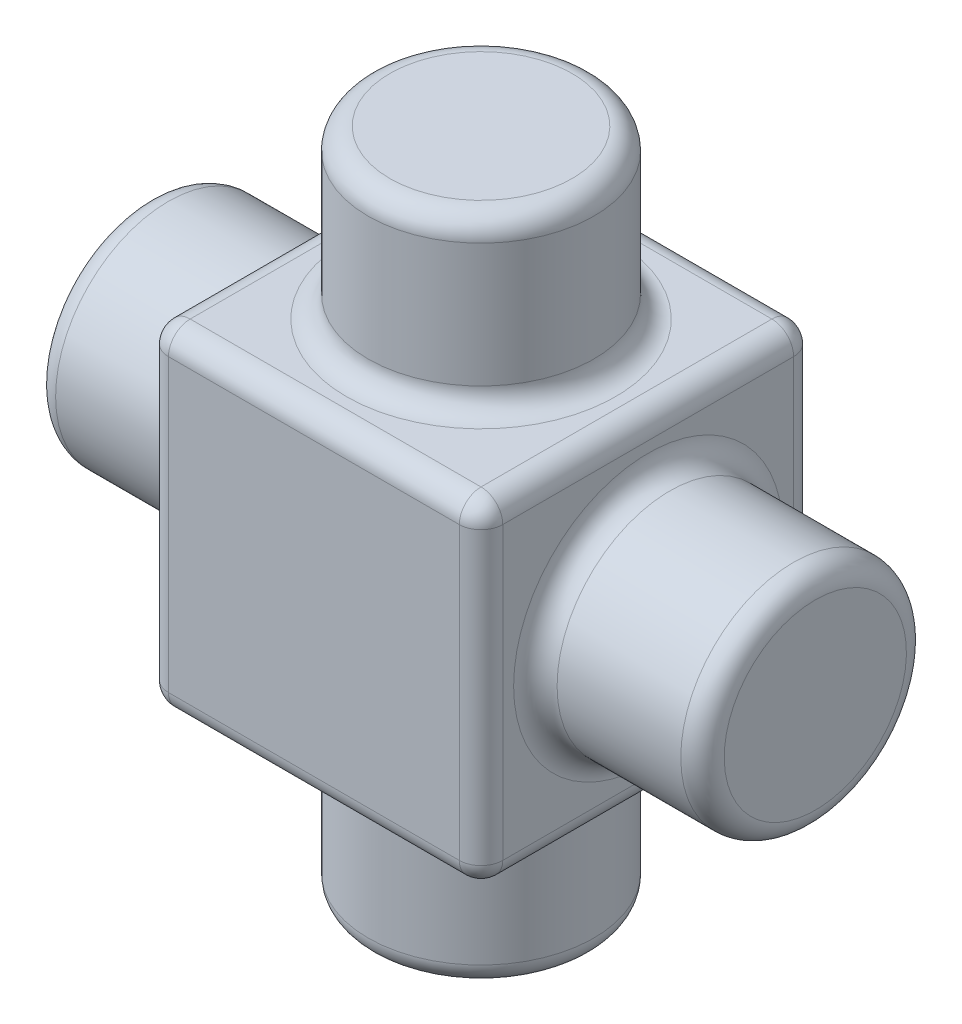
SolidWorks part; units mm, degrees
material "Brass"
ref_plane "Front Plane" through (0, 0, 0) normal (0, 0, 1) x (1, 0, 0)
ref_plane "Top Plane" through (0, 0, 0) normal (0, 1, 0) x (1, 0, 0)
ref_plane "Right Plane" through (0, 0, 0) normal (1, 0, 0) x (0, 0, -1)
sketch "Sketch1" plane through (0, 0, 0) normal (0, 1, 0) x (1, 0, 0)
  line L1 (-25.4, -25.4) -> (25.4, -25.4)
  line L2 (-25.4, -25.4) -> (-25.4, 25.4)
  line L3 (-25.4, 25.4) -> (25.4, 25.4)
  line L4 (25.4, -25.4) -> (25.4, 25.4)
  line L5 (-25.4, -25.4) -> (25.4, 25.4) construction
  line L6 (-25.4, 25.4) -> (25.4, -25.4) construction
  circle A0 centre (0, 0) radius 17.145
  dimension "D2" = 34.29
  dimension "D1" = 50.8
extrude "Boss-Extrude1" add sketch "Sketch1" along normal mid plane 50.8 contours A0 | L1 L4 L3 L2 A0 region at (-24.6816, 0, 0) region at (0, 0, 0)
extrude "Boss-Extrude2" add sketch "Sketch1<3>" along normal mid plane 101.6 contours A0 region at (0, 0, 0)
sketch "Sketch1<3>" plane through (0, 0, 0) normal (0, 1, 0) x (1, 0, 0) same geometry as "Sketch1"
ref_plane "Plane1" through (0, 0, 0) normal (-0.7071, 0.7071, 0) x (0.7071, 0.7071, 0)
mirror "Mirror1" about plane through (0, 0, 0) normal (-0.7071, 0.7071, 0) of "Boss-Extrude2"
fillet "Fillet1" radius 3.302 20 edges at (0, -50.8, 17.145) (50.8, 0, 17.145) (0, 50.8, 17.145) (-50.8, 0, 17.145) (0, -25.4, 17.145) (-25.4, -25.4, 0) (-25.4, 0, 17.145) (-25.4, 0, -25.4) (0, -25.4, -25.4) (25.4, 0, -25.4) (25.4, -25.4, 0) (25.4, 0, 17.145) (-25.4, 25.4, 0) (0, 25.4, -25.4) (25.4, 25.4, 0) (0, 25.4, 17.145) (-25.4, 0, 25.4) (0, 25.4, 25.4) (25.4, 0, 25.4) (0, -25.4, 25.4)
